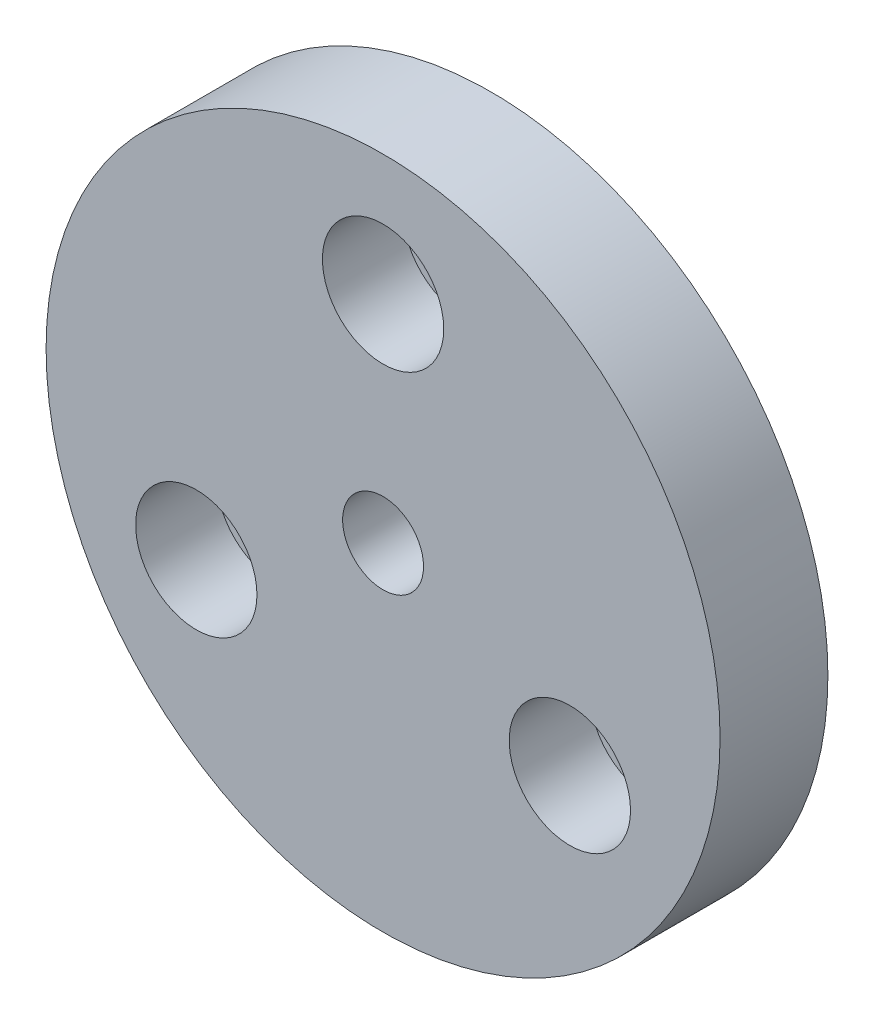
SolidWorks part; units mm, degrees
ref_plane "前视基准面" through (0, 0, 0) normal (0, 0, 1) x (1, 0, 0)
ref_plane "上视基准面" through (0, 0, 0) normal (0, 1, 0) x (1, 0, 0)
ref_plane "右视基准面" through (0, 0, 0) normal (1, 0, 0) x (0, 0, -1)
other "Configuration Table"
sketch "草图1" plane through (0, 0, 0) normal (0, 0, 1) x (1, 0, 0)
  line L0 (0, 0) -> (1.6914, 0.6156) construction
  line L1 (0, 0) -> (1.5832, 0.5954)
  line L2 (0, 0) -> (1.5832, -0.5954)
  line L3 (0, 0) -> (1.6914, -0.6156) construction
  line L4 (0, 0) -> (2.55, 0) construction
  line L5 (1.6914, 0.6156) -> (1.6914, -0.6156) construction
  circle A0 centre (0, 0) radius 1.65
  circle A1 centre (0, 0) radius 2.55
  circle A2 centre (0, 0) radius 1.6914 construction
  circle A3 centre (0, 0) radius 1.8 construction
  circle A4 centre (0, 0) radius 3
  spline S0 degree 4 poles (1.5832, 0.5954) (1.5953, 0.5999) (1.6299, 0.61) (1.6985, 0.6188) (1.8107, 0.6176) (1.9542, 0.5935) (2.1323, 0.5368) (2.3288, 0.4397) (2.527, 0.3033) (2.7182, 0.1281) (2.8863, -0.0692) (3.0309, -0.2841) (3.1583, -0.5243) (3.284, -0.8365) (3.3855, -1.2255) (3.4358, -1.6902) (3.4119, -2.2085) (3.3126, -2.7182) (3.1474, -3.2089) (2.918, -3.6756) (2.6387, -4.1089) (2.3029, -4.5102) (1.9385, -4.866) (1.5141, -5.1906) (1.1742, -5.4065) (0.7714, -5.6132) (0.5343, -5.7151) (0.2601, -5.8236) (0.1183, -5.8645) (-0.005, -5.9055) (-0.0434, -5.9147) (-0.0704, -5.9226) (-0.0848, -5.927) knots 0 0 0 0 0 0.005604 0.015718 0.02996 0.048734 0.068727 0.096889 0.125051 0.153212 0.181374 0.209535 0.237696 0.271429 0.327752 0.384075 0.440398 0.496721 0.553044 0.609367 0.66569 0.722013 0.778336 0.834659 0.890982 0.909091 0.954545 0.977273 0.988636 0.994318 1 1 1 1 1 construction
  spline S1 degree 4 poles (1.5832, 0.5954) (1.5953, 0.5999) (1.6299, 0.61) (1.6985, 0.6188) (1.8107, 0.6176) (1.9542, 0.5935) (2.1323, 0.5368) (2.3288, 0.4397) (2.527, 0.3033) (2.7182, 0.1281) (2.8863, -0.0692) (3.0309, -0.2841) (3.1583, -0.5243) (3.284, -0.8365) (3.3855, -1.2255) (3.4358, -1.6902) (3.4119, -2.2085) (3.3126, -2.7182) (3.1474, -3.2089) (2.918, -3.6756) (2.6387, -4.1089) (2.3029, -4.5102) (1.9385, -4.866) (1.5141, -5.1906) (1.1742, -5.4065) (0.8753, -5.5599) (0.734, -5.626) (0.6996, -5.6416) knots 0 0 0 0 0 0.005604 0.015718 0.02996 0.048734 0.068727 0.096889 0.125051 0.153212 0.181374 0.209535 0.237696 0.271429 0.327752 0.384075 0.440398 0.496721 0.553044 0.609367 0.66569 0.722013 0.778336 0.834659 0.890982 0.909091 0.909091 0.909091 0.909091 0.909091
  spline S2 degree 4 poles (1.5832, -0.5954) (1.5953, -0.5999) (1.6299, -0.61) (1.6985, -0.6188) (1.8107, -0.6176) (1.9542, -0.5935) (2.1323, -0.5368) (2.3288, -0.4397) (2.527, -0.3033) (2.7182, -0.1281) (2.8863, 0.0692) (3.0309, 0.2841) (3.1583, 0.5243) (3.284, 0.8365) (3.3855, 1.2255) (3.4358, 1.6902) (3.4119, 2.2085) (3.3126, 2.7182) (3.1474, 3.2089) (2.918, 3.6756) (2.6387, 4.1089) (2.3029, 4.5102) (1.9385, 4.866) (1.5141, 5.1906) (1.1742, 5.4065) (0.7714, 5.6132) (0.5343, 5.7151) (0.2601, 5.8236) (0.1183, 5.8645) (-0.005, 5.9055) (-0.0434, 5.9147) (-0.0704, 5.9226) (-0.0848, 5.927) knots 0 0 0 0 0 0.005604 0.015718 0.02996 0.048734 0.068727 0.096889 0.125051 0.153212 0.181374 0.209535 0.237696 0.271429 0.327752 0.384075 0.440398 0.496721 0.553044 0.609367 0.66569 0.722013 0.778336 0.834659 0.890982 0.909091 0.954545 0.977273 0.988636 0.994318 1 1 1 1 1 construction
  spline S3 degree 4 poles (1.5832, -0.5954) (1.5953, -0.5999) (1.6299, -0.61) (1.6985, -0.6188) (1.8107, -0.6176) (1.9542, -0.5935) (2.1323, -0.5368) (2.3288, -0.4397) (2.527, -0.3033) (2.7182, -0.1281) (2.8863, 0.0692) (3.0309, 0.2841) (3.1583, 0.5243) (3.284, 0.8365) (3.3855, 1.2255) (3.4358, 1.6902) (3.4119, 2.2085) (3.3126, 2.7182) (3.1474, 3.2089) (2.918, 3.6756) (2.6387, 4.1089) (2.3029, 4.5102) (1.9385, 4.866) (1.5141, 5.1906) (1.1742, 5.4065) (0.8753, 5.5599) (0.734, 5.626) (0.6996, 5.6416) knots 0 0 0 0 0 0.005604 0.015718 0.02996 0.048734 0.068727 0.096889 0.125051 0.153212 0.181374 0.209535 0.237696 0.271429 0.327752 0.384075 0.440398 0.496721 0.553044 0.609367 0.66569 0.722013 0.778336 0.834659 0.890982 0.909091 0.909091 0.909091 0.909091 0.909091
  point P16 (1.6914, 0)
  dimension "内啮合齿顶圆直径" = 3.3
  dimension "内啮合分度圆直径" = 3.6
  dimension "内啮合基圆直径" = 3.3829
  dimension "内啮合齿根圆直径" = 5.1
  dimension "外径" = 6
  dimension "渐开线镜像线夹角" = 20
extrude "凸台-拉伸1" add sketch "草图1" along normal blind 4 contours A4 | A0
extrude "切除-拉伸2" cut sketch "草图1<3>" along normal through all contours A0 S3 A1 S1 region at (2.0287, 0, 0)
sketch "草图1<3>" plane through (0, 0, 0) normal (0, 0, 1) x (1, 0, 0) same geometry as "草图1"
pattern_circular "阵列(圆周)1" count 9 over 360 about axis through (0, 0, 4) along (0, 0, 1) of "切除-拉伸2"
sketch "草图2" plane through (0, 0, 0) normal (0, 0, -1) x (-1, 0, 0)
  circle A0 centre (0, 0) radius 3
  circle A1 centre (0, 0) radius 3 construction
  circle A2 centre (0, 0) radius 5
  dimension "D1" = 10
extrude "凸台-拉伸2" add sketch "草图2" against normal up to surface (4 mm away) contours A2 up to face at (3, 0, 4)
sketch "草图3" plane through (0, 0, 0) normal (0, 0, 1) x (1, 0, 0)
  circle A0 centre (0, 8) radius 2.25
  circle A1 centre (0, 8) radius 1.5
  circle A2 centre (0, 0) radius 12.5
  circle A3 centre (6.9282, -4) radius 1.5
  circle A4 centre (6.9282, -4) radius 2.25
  circle A5 centre (-6.9282, -4) radius 1.5
  circle A6 centre (-6.9282, -4) radius 2.25
  circle A7 centre (0, 0) radius 5
  circle A10 centre (0, 0) radius 5 construction
  point P14 (0, 0)
  dimension "D4" = 3
  dimension "D5" = 4.5
  dimension "D1" = 25
  dimension "D2" = 3
  dimension "D3" = 8
extrude "凸台-拉伸4" add sketch "草图3" along normal blind 4 contours A2 | A5 | A3 | A1 | A7
extrude "切除-拉伸3" cut sketch "草图3<3>" against normal offset from surface (3 mm away) 1 from surface contours A0 | A4 | A6 up to face at (12.5, 0, 0) starting at face at (1.5, 8, 4)
sketch "草图3<3>" plane through (0, 0, 0) normal (0, 0, 1) x (1, 0, 0) same geometry as "草图3"
sketch "草图4" plane through (0, 0, 4) normal (0, 0, 1) x (1, 0, 0)
  circle A0 centre (0, 0) radius 1.5
  dimension "D1" = 3
extrude "切除-拉伸4" cut sketch "草图4" against normal through all
equation "\"m\"= 0.4'模数"
equation "\"z1\"= 9'外啮合齿轮数"
equation "\"a\"= 20度'压力角"
equation "\"z2\"= 9'内啮合齿轮数"
equation "\"hax\"= 1'齿顶高系数"
equation "\"cx\"= 0.25'顶隙系数"
equation "\"ha\"= \"hax\" * \"m\"'齿顶高"
equation "\"hf\"= ( \"hax\" + \"cx\" ) * \"m\"'齿根高"
equation "\"d1\"= \"m\" * \"z1\"'外啮合分度圆直径"
equation "\"da1\"= ( \"z1\" + 2 ) * \"m\"'外啮合齿顶圆直径"
equation "\"df1\"= \"d1\" - 2 * \"hf\"'外啮合齿根圆直径"
equation "\"db1\"= \"d1\" * cos ( \"a\" )'外啮合基圆直径"
equation "\"p\"= \"m\" * PI'齿距"
equation "\"d2\"= \"m\" * \"z2\"'内啮合分度圆直径"
equation "\"db2\"= \"d2\" * cos ( \"a\" )'内啮合基圆直径"
equation "\"da2\"= ( \"z2\" - 2 ) * \"m\"'内啮合齿顶圆直径"
equation "\"df2\"= \"d2\" + 2 * \"hf\"'内啮合齿根圆直径"
equation "\"内啮合齿顶圆直径@草图1\" = \"da2\" + 1 * \"hf\""
equation "\"内啮合齿根圆直径@草图1\" = \"df2\" + 1 * \"hf\""
equation "\"内啮合分度圆直径@草图1\"= \"d2\""
equation "\"内啮合基圆直径@草图1\"= \"db2\""
equation "\"渐开线镜像线夹角@草图1\"= 360度 / 4 / \"z2\" + 360度 / 4 / \"z2\""
equation "\"do\"= IIF ( \"edo\" >= ( \"df2\" + 1 ) , \"edo\" , ( \"df2\" + 1 ) )'外圈直径"
equation "\"h\"= 4'厚度"
equation "\"外径@草图1\"= \"do\""
equation "\"厚度@凸台-拉伸1\"= \"h\""
equation "\"内啮合齿轮数@阵列(圆周)1\"= \"z2\""
equation "\"edo\"= 6'期望的外圈直径"
